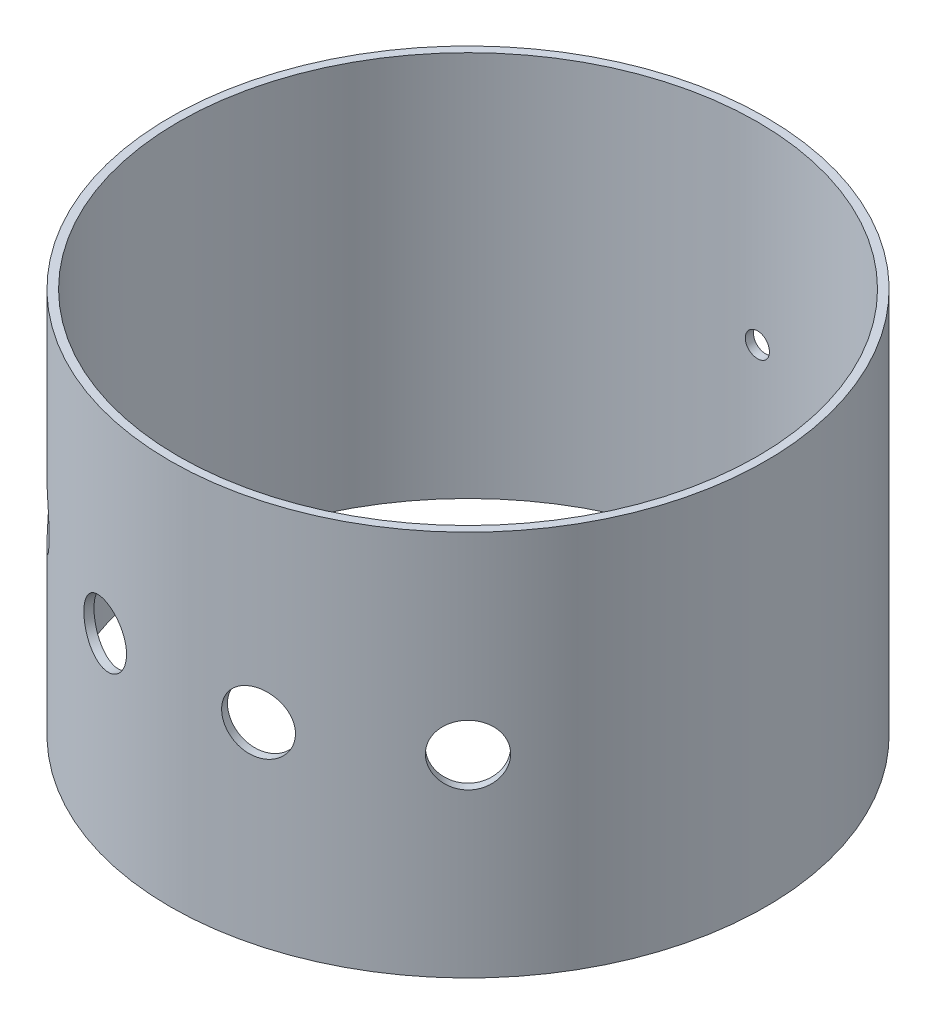
SolidWorks part; units mm, degrees
material "C-Glass Fiber"
ref_plane "Front Plane" through (0, 0, 0) normal (0, 0, 1) x (1, 0, 0)
ref_plane "Top Plane" through (0, 0, 0) normal (0, 1, 0) x (1, 0, 0)
ref_plane "Right Plane" through (0, 0, 0) normal (1, 0, 0) x (0, 0, -1)
sketch "Body Tube Profile" plane through (0, 0, 0) normal (0, 1, 0) x (1, 0, 0)
  circle A0 centre (0, 0) radius 76.2
  circle A1 centre (0, 0) radius 78.359
  dimension "D1" = 152.4
  dimension "D2" = 156.718
extrude "Body Tube Extrustion" add sketch "Body Tube Profile" along normal blind 101.6
sketch "Center Axis" plane through (0, 0, 0) normal (0, 0, 1) x (1, 0, 0)
  line L0 (0, 0) -> (0, 101.6) construction
  line L1 (76.2, 101.6) -> (-76.2, 101.6) construction
ref_plane "Offset Cut Plane" through (0, 0, 0) normal (0.7071, 0, 0.7071) x (0, 1, 0)
sketch "Sketch2" plane through (0, 0, 0) normal (0.7071, 0, 0.7071) x (0, 1, 0)
  line L0 (50.8, 78.359) -> (50.8, -78.359) construction
  line L1 (101.6, 78.359) -> (0, 78.359) construction
  line L2 (0, -78.359) -> (101.6, -78.359) construction
  circle A0 centre (50.8, 0) radius 7.9375
  dimension "D1" = 15.875
extrude "Key Hole Cut" cut sketch "Sketch2" along normal through all
pattern_circular "Key Hole Pattern" count 4 over 90 about axis through (0, 101.6, 0) along (0, 1, 0) of "Key Hole Cut" reverse direction yes
sketch "Sketch3" plane through (0, 0, 0) normal (0, 0, 1) x (1, 0, 0)
  line L0 (-78.359, 50.8) -> (78.359, 50.8) construction
  line L1 (-78.359, 101.6) -> (-78.359, 0) construction
  line L2 (78.359, 0) -> (78.359, 101.6) construction
  circle A0 centre (0, 50.8) radius 3.175
  dimension "D1" = 6.35
extrude "Cut-Extrude1" cut sketch "Sketch3" against normal through all
ref_plane "Plane1" through (0, 50.8, 0) normal (0, 1, 0) x (1, 0, 0)
sketch "Sketch5" plane through (0, 50.8, 0) normal (0, 1, 0) x (1, 0, 0)
  line L0 (0, 0) -> (0, 77.2795) construction
  line L2 (0, 0.0889) -> (0, 0)
  line L3 (0, 0) -> (54.6449, -54.6449)
  line L4 (0, 0.1778) -> (0, -77.1017) construction
  dimension "D2" = 77.2795
equation "\"Length\"=4"
equation "\"Outer Diameter\"= 6.17"
equation "\"Inner Diameter\"= 6"
equation "\"Wall Thickness\"= 0.085"
equation "\"D1@Body Tube Profile\" = \"Inner Diameter\""
equation "\"D2@Body Tube Profile\" = \"Outer Diameter\""
equation "\"D1@Body Tube Extrustion\" = \"Length\""
equation "\"Key Hole Dia\"= 0.625"
equation "\"Hole Angle 1\"= 15"
equation "\"Hole Angle 2\"= 45"
equation "\"D1@Sketch2\"=\"Key Hole Dia\""
